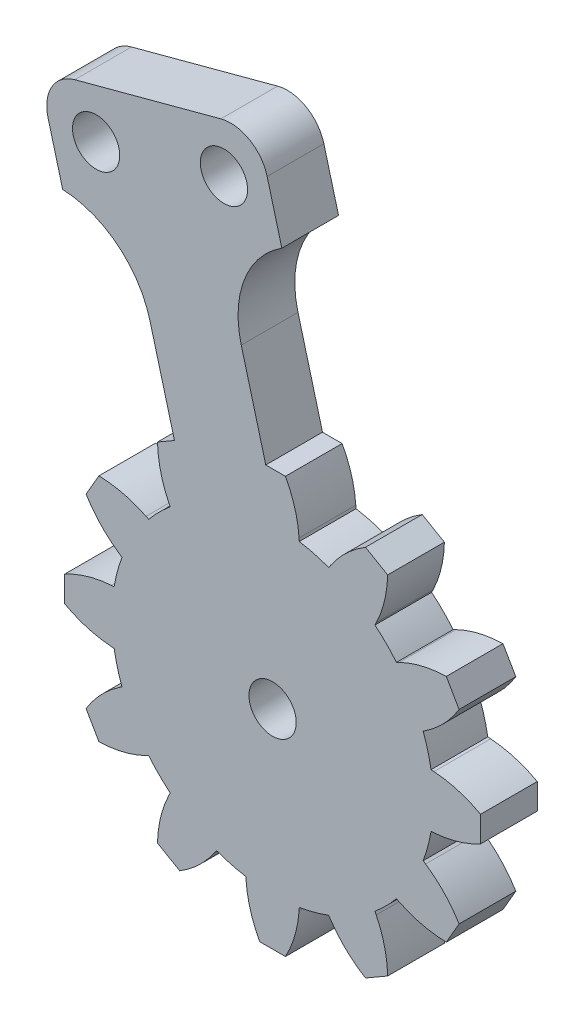
SolidWorks part; units mm, degrees
ref_plane "Front Plane" through (0, 0, 0) normal (0, 0, 1) x (1, 0, 0)
ref_plane "Top Plane" through (0, 0, 0) normal (0, 1, 0) x (1, 0, 0)
ref_plane "Right Plane" through (0, 0, 0) normal (1, 0, 0) x (0, 0, -1)
sketch "Sketch1" plane through (0, 0, 0) normal (0, 0, 1) x (1, 0, 0)
  circle A0 centre (0, 0) radius 8.5
  dimension "D1" = 17
extrude "Boss-Extrude1" add sketch "Sketch1" along normal blind 3
sketch "Sketch2" plane through (0, 0, 3) normal (0, 0, 1) x (1, 0, 0)
  line L0 (0, 0) -> (0, 12.8785) construction
  line L1 (0, 0) -> (1.4399, 10.9374) construction
  line L2 (0, 0) -> (-1.4446, 10.9725) construction
  line L3 (0, 0) -> (-3.4108, 12.7294) construction
  circle A0 centre (0, 0) radius 10 construction
  circle A1 centre (0, 0) radius 2.5 construction
  dimension "D3" = 20
  dimension "D5" = 5
  dimension "D1" = 7.5
  dimension "D2" = 7.5
  dimension "D4" = 15
ref_point "Point3"
ref_point "Point4"
sketch "Sketch3" plane through (0, 0, 3) normal (0, 0, 1) x (1, 0, 0)
  line L0 (-1.3053, 9.9144) -> (-1.5091, 7)
  line L1 (-1.5091, 7) -> (1.5091, 7)
  line L2 (1.3053, 9.9144) -> (1.5091, 7)
  line L3 (1.3053, 9.9144) -> (0.6785, 11)
  line L4 (-1.3053, 9.9144) -> (-0.6785, 11)
  line L5 (-0.6785, 11) -> (0.6785, 11)
  dimension "D1" = 11
  dimension "D2" = 7
  dimension "D3" = 60
  dimension "D4" = 86
  dimension "D5" = 60
  dimension "D6" = 86
extrude "Boss-Extrude2" add sketch "Sketch3" against normal blind 3
pattern_circular "CirPattern2" count 12 over 360 about axis through (0, 0, 3) along (0, 0, -1) of "Boss-Extrude2"
fillet "Fillet5" radius 6 12 edges at (9.2388, 3.8268, 1.5) (6.0876, 7.9335, 1.5) (1.3053, 9.9144, 1.5) (-3.8268, 9.2388, 1.5) (-7.9335, 6.0876, 1.5) (-9.9144, 1.3053, 1.5) (-9.2388, -3.8268, 1.5) (-6.0876, -7.9335, 1.5) (-1.3053, -9.9144, 1.5) (3.8268, -9.2388, 1.5) (7.9335, -6.0876, 1.5) (9.9144, -1.3053, 1.5)
fillet "Fillet6" radius 6 12 edges at (7.9335, 6.0876, 1.5) (3.8268, 9.2388, 1.5) (-1.3053, 9.9144, 1.5) (-6.0876, 7.9335, 1.5) (-9.2388, 3.8268, 1.5) (-9.9144, -1.3053, 1.5) (-7.9335, -6.0876, 1.5) (-3.8268, -9.2388, 1.5) (1.3053, -9.9144, 1.5) (6.0876, -7.9335, 1.5) (9.2388, -3.8268, 1.5) (9.9144, 1.3053, 1.5)
sketch "Sketch12" plane through (0, 0, 0) normal (0, 0, -1) x (-1, 0, 0)
  line L0 (0, 0) -> (0, 13.7449) construction
  line L1 (0, 0) -> (3.8761, 14.4659) construction
  line L2 (1.5359, 15.3913) -> (-4.2265, -6.1144)
  line L3 (-4.2265, -6.1144) -> (0.6031, -7.4085)
  line L4 (0.6031, -7.4085) -> (9.0147, 23.9841)
  line L5 (1.5359, 15.3913) -> (4.1851, 25.2782)
  line L6 (4.1851, 25.2782) -> (9.0147, 23.9841)
  circle A0 centre (0, 0) radius 2.5 construction
  dimension "D2" = 5
  dimension "D1" = 15
  dimension "D3" = 15
  dimension "D4" = 90
  dimension "D5" = 90
  dimension "D6" = 2.5
  dimension "D7" = 5
  dimension "D8" = 2.5
  dimension "D9" = 7
  dimension "D10" = 25.5
extrude "Boss-Extrude5" add sketch "Sketch12" against normal blind 3
sketch "Sketch14" plane through (0, 0, 0) normal (0, 0, -1) x (-1, 0, 0)
  circle A0 centre (0, 0) radius 1.25
  dimension "D1" = 2.5
sketch "Sketch15" plane through (0, 0, 0) normal (0, 0, -1) x (-1, 0, 0)
  circle A0 centre (0, 0) radius 5
  dimension "D1" = 10
extrude "Boss-Extrude6" add sketch "Sketch15" against normal blind 1.9
extrude "Cut-Extrude7" cut sketch "Sketch14" against normal through all
sketch "Sketch17" plane through (0, 0, 3) normal (0, 0, 1) x (1, 0, 0)
  circle A0 centre (-5.9528, 22.2163) radius 1.25
  circle A1 centre (0, 0) radius 1.25 construction
  dimension "D1" = 2.5
  dimension "D2" = 23
extrude "Cut-Extrude9" cut sketch "Sketch17" against normal through all
ref_axis "Axis1" through (0, 0, 3) along (0, 0, -1)
sketch "Sketch18" plane through (0, 0, 0) normal (0, 0, 1) x (1, 0, 0)
  line L0 (0, 0) -> (8.2104, 2.2) construction
  arc A0 (8.3818, 1.4124) -> (7.9651, 2.9677) centre (0, 0) ccw construction
fillet "Fillet7" radius 2.5 2 edges at (-9.0147, 23.9841, 1.5) (-4.1851, 25.2782, 1.5)
sketch "Sketch19" plane through (0, 0, 3) normal (0, 0, 1) x (1, 0, 0)
  line L0 (-6.5999, 24.6311) -> (-12.3954, 23.0782)
  line L1 (-12.3954, 23.0782) -> (-11.1013, 18.2486)
  line L2 (-11.1013, 18.2486) -> (0.4898, 21.3544)
  line L3 (0.4898, 21.3544) -> (-0.8043, 26.184)
  line L4 (-0.8043, 26.184) -> (-6.5999, 24.6311)
  dimension "D1" = 6
  dimension "D2" = 6
  dimension "D3" = 5
extrude "Boss-Extrude7" add sketch "Sketch19" against normal blind 3
sketch "Sketch20" plane through (0, 0, 3) normal (0, 0, 1) x (1, 0, 0)
  line L0 (-12.3954, 23.0782) -> (-11.1013, 18.2486) construction
  line L1 (-0.8043, 26.184) -> (-12.3954, 23.0782) construction
  line L3 (0.4898, 21.3544) -> (-0.8043, 26.184) construction
  circle A0 centre (-9.3336, 21.3104) radius 1.25
  circle A1 centre (-2.5721, 23.1222) radius 1.25
  point P8 (0, 0)
  point P10 (-0.547, 25.2237)
  dimension "D5" = 2.5
  dimension "D6" = 2.5
  dimension "D1" = 2.5
  dimension "D2" = 2.5
  dimension "D3" = 2.5
  dimension "D4" = 2.5
extrude "Cut-Extrude10" cut sketch "Sketch20" against normal blind 3
fillet "Fillet8" radius 5 1 edges at (-7.7206, 19.1544, 1.5)
fillet "Fillet9" radius 5 1 edges at (-2.891, 20.4485, 1.5)
fillet "Fillet10" radius 2 1 edges at (-0.8043, 26.184, 1.5)
fillet "Fillet11" radius 2 1 edges at (-12.3954, 23.0782, 1.5)
